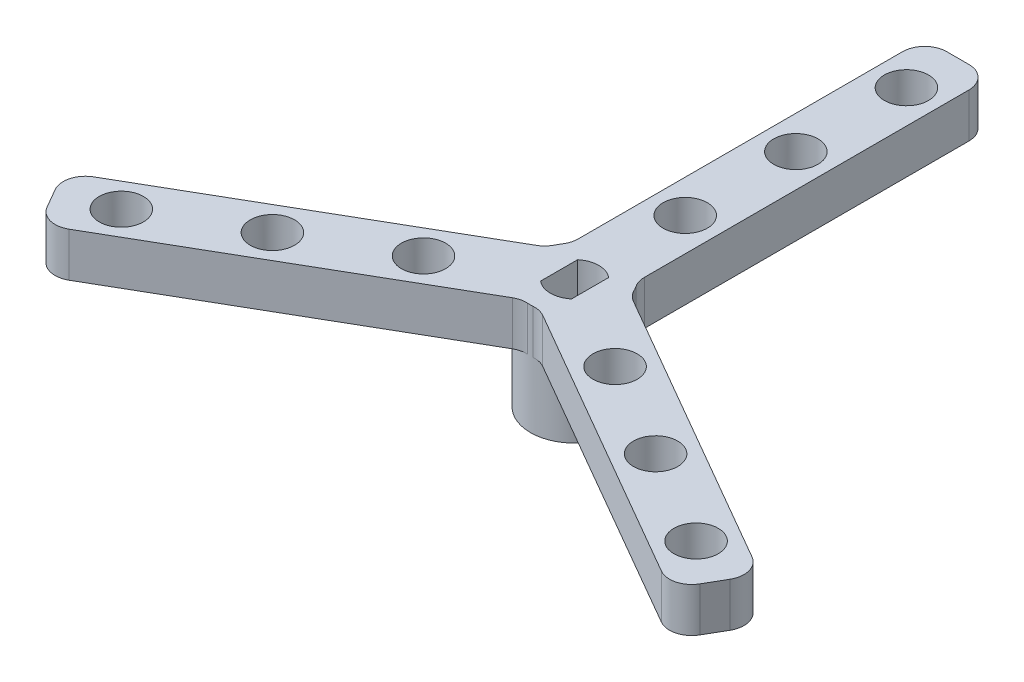
SolidWorks part; units mm, degrees
material "ABS"
ref_plane "Front Plane" through (0, 0, 0) normal (0, 0, 1) x (1, 0, 0)
ref_plane "Top Plane" through (0, 0, 0) normal (0, 1, 0) x (1, 0, 0)
ref_plane "Right Plane" through (0, 0, 0) normal (1, 0, 0) x (0, 0, -1)
sketch "Sketch1" plane through (0, 0, 0) normal (0, 1, 0) x (1, 0, 0)
  line L0 (1.7875, 5.8114) -> (1.7875, 1.6201)
  line L2 (-1.3625, 5.6407) -> (-1.3625, 1.7907)
  line L4 (1.4375, 5.6407) -> (1.4375, 1.7907)
  line L5 (-1.7125, 5.8114) -> (-1.7125, 1.6201)
  arc A1 (-1.3625, 5.6407) -> (1.4375, 5.6407) centre (0.0375, 3.7161) cw
  arc A2 (-1.3625, 1.7907) -> (1.4375, 1.7907) centre (0.0375, 3.7154) ccw
  arc A3 (-1.7125, 5.8114) -> (1.7875, 5.8114) centre (0.0375, 3.7161) cw
  arc A4 (-1.7125, 1.6201) -> (1.7875, 1.6201) centre (0.0375, 3.7154) ccw
  circle A5 centre (0.0375, 3.7154) radius 5
  dimension "D1" = 3.85
  dimension "D3" = 2.38
  dimension "D4" = 2.38
  dimension "D6" = 10
  dimension "D2" = 2.8
  dimension "D5" = 0.35
extrude "Boss-Extrude1" add sketch "Sketch1" along normal blind 12.5 contours A5 A4 L5 A3 L0 region at (-4.8211, 0, -3.7154)
sketch "Sketch2" plane through (0, 12.5, 0) normal (0, 1, 0) x (1, 0, 0)
  line L0 (0.0375, 47.0226) -> (0.0375, 7.0226) construction
  line L1 (0.0375, 8.7154) -> (0.0375, 9.9323) construction
  line L2 (4.7766, 5.3094) -> (1.0266, -1.1858)
  line L3 (-3.7125, 7.0226) -> (3.7875, 7.0226)
  line L4 (-3.7125, 7.0226) -> (-3.7125, 47.0226)
  line L5 (3.7875, 7.0226) -> (3.7875, 47.0226)
  line L6 (-3.7125, 47.0226) -> (3.7875, 47.0226)
  line L7 (4.7766, 5.3094) -> (39.4176, -14.6906)
  line L8 (1.0266, -1.1858) -> (35.6676, -21.1858)
  line L9 (39.4176, -14.6906) -> (35.6676, -21.1858)
  line L10 (37.5426, -17.9382) -> (2.9016, 2.0618) construction
  line L11 (-4.7016, 5.3094) -> (-0.9516, -1.1858)
  line L12 (-4.7016, 5.3094) -> (-39.3427, -14.6906)
  line L13 (-0.9516, -1.1858) -> (-35.5927, -21.1858)
  line L14 (-39.3427, -14.6906) -> (-35.5927, -21.1858)
  line L15 (-2.8266, 2.0618) -> (-37.4677, -17.9382) construction
  circle A0 centre (0.0375, 3.7154) radius 5 construction
  point P6 (0.0375, 3.7154)
  dimension "D1" = 7.5
  dimension "D2" = 40
  dimension "D3" = 0
  dimension "D4" = 7.5
  dimension "D5" = 40
  dimension "D6" = 120
  dimension "D7" = 7.5
  dimension "D8" = 40
  dimension "D9" = 120
extrude "Boss-Extrude4" add sketch "Sketch2" against normal blind 5
sketch "Sketch4" plane through (0, 12.5, 0) normal (0, 1, 0) x (1, 0, 0)
  line L0 (3.7875, 7.0226) -> (3.7875, 47.0226) construction
  line L1 (0.0375, 3.7161) -> (37.5426, -17.9382) construction
  line L2 (35.6676, -21.1858) -> (39.4176, -14.6906) construction
  line L3 (0.0375, 3.7161) -> (-37.4677, -17.9382) construction
  line L4 (-39.3427, -14.6906) -> (-35.5927, -21.1858) construction
  circle A0 centre (0.0375, 16.2161) radius 2.5
  circle A1 centre (0.0375, 28.7161) radius 2.5
  circle A2 centre (0.0375, 41.2161) radius 2.5
  circle A3 centre (-10.788, -2.5337) radius 2.5
  circle A4 centre (-21.6135, -8.7834) radius 2.5
  circle A5 centre (-32.439, -15.0331) radius 2.5
  circle A6 centre (10.8629, -2.5337) radius 2.5
  circle A7 centre (21.6884, -8.7834) radius 2.5
  circle A8 centre (32.5139, -15.0331) radius 2.5
  point P5 (0.0375, 3.7161)
  dimension "D1" = 5
  dimension "D2" = 5
  dimension "D7" = 5
  dimension "D3" = 12.5
  dimension "D4" = 12.5
  dimension "D5" = 3.75
  dimension "D6" = 3.75
  dimension "D8" = 3.75
  dimension "D9" = 12.5
extrude "Cut-Extrude1" cut sketch "Sketch4" against normal blind 100
fillet "Fillet1" radius 2.5 6 edges at (4.7766, 10, -5.3094) (3.7875, 10, -7.0226) (-3.7125, 10, -7.0226) (-4.7016, 10, -5.3094) (-0.9516, 10, 1.1858) (1.0266, 10, 1.1858)
fillet "Fillet2" radius 2.5 6 edges at (-3.7125, 10, -47.0226) (3.7875, 10, -47.0226) (39.4176, 10, 14.6906) (35.6676, 10, 21.1858) (-39.3427, 10, 14.6906) (-35.5927, 10, 21.1858)
